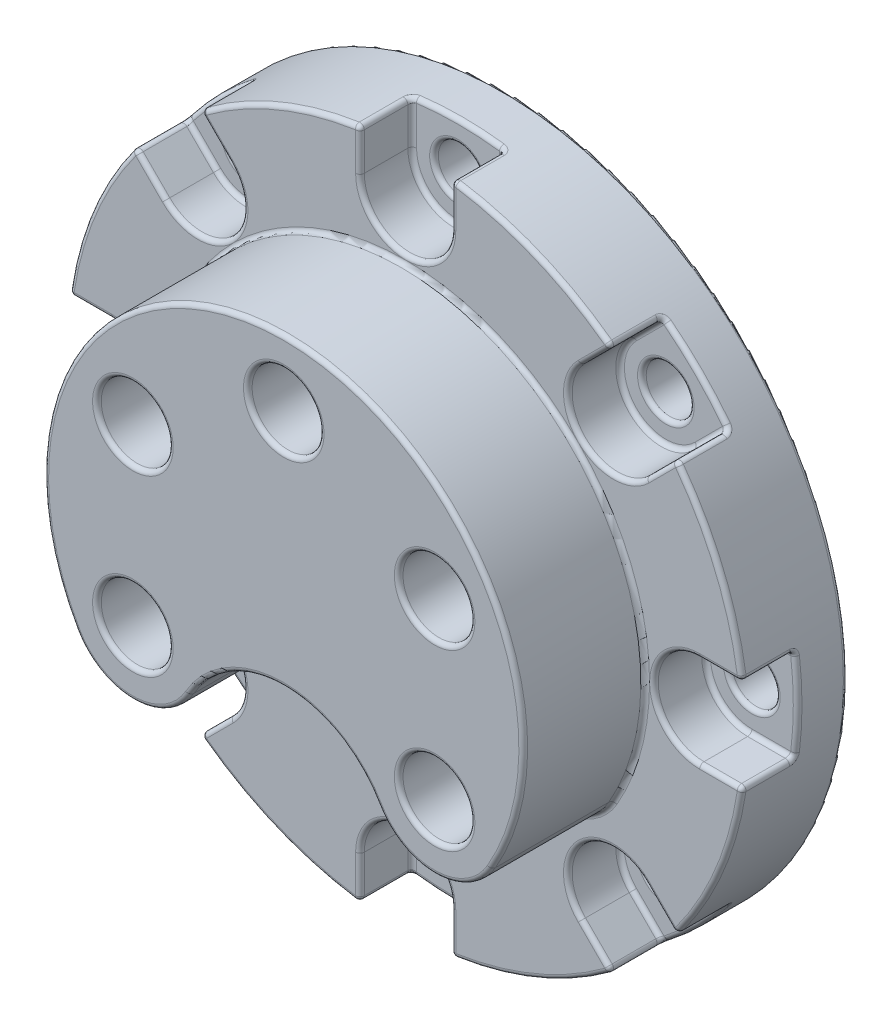
SolidWorks part; units mm, degrees
ref_plane "정면" through (0, 0, 0) normal (0, 0, 1) x (1, 0, 0)
ref_plane "윗면" through (0, 0, 0) normal (0, 1, 0) x (1, 0, 0)
ref_plane "우측면" through (0, 0, 0) normal (1, 0, 0) x (0, 0, -1)
sketch "스케치1" plane through (0, 0, 0) normal (0, 0, 1) x (1, 0, 0)
  circle A0 centre (0, 0) radius 15.6
  circle A1 centre (0, 13.5) radius 1.1
  circle A2 centre (9.5459, 9.5459) radius 1.1
  circle A3 centre (13.5, 0) radius 1.1
  circle A4 centre (9.5459, -9.5459) radius 1.1
  circle A5 centre (0, -13.5) radius 1.1
  circle A6 centre (-9.5459, -9.5459) radius 1.1
  circle A7 centre (-13.5, 0) radius 1.1
  circle A8 centre (-9.5459, 9.5459) radius 1.1
  point P22 (0, 0)
  dimension "D1" = 31.2
  dimension "D2" = 2.2
  dimension "D3" = 13.5
  dimension "D4" = 8
extrude "보스-돌출1" add sketch "스케치1" along normal blind 4.7 contours A0 A8 A7 A6 A5 A4 A3 A2 A1 region at (0, 0, 0)
sketch "스케치2" plane through (0, 0, 4.7) normal (0, 0, 1) x (1, 0, 0)
  line L0 (-2.1, 13.5) -> (-2.1, 15.458)
  line L1 (2.1, 13.5) -> (2.1, 15.458)
  line L2 (11.0309, 8.061) -> (12.4154, 9.4455)
  line L3 (8.061, 11.0309) -> (9.4455, 12.4154)
  line L4 (13.5, -2.1) -> (15.458, -2.1)
  line L5 (13.5, 2.1) -> (15.458, 2.1)
  line L6 (8.061, -11.0309) -> (9.4455, -12.4154)
  line L7 (11.0309, -8.061) -> (12.4154, -9.4455)
  line L8 (-2.1, -13.5) -> (-2.1, -15.458)
  line L9 (2.1, -13.5) -> (2.1, -15.458)
  line L10 (-11.0309, -8.061) -> (-12.4154, -9.4455)
  line L11 (-8.061, -11.0309) -> (-9.4455, -12.4154)
  line L12 (-13.5, 2.1) -> (-15.458, 2.1)
  line L13 (-13.5, -2.1) -> (-15.458, -2.1)
  line L14 (-8.061, 11.0309) -> (-9.4455, 12.4154)
  line L15 (-11.0309, 8.061) -> (-12.4154, 9.4455)
  arc A0 (-2.1, 13.5) -> (2.1, 13.5) centre (0, 13.5) ccw
  circle A1 centre (0, 0) radius 15.6 construction
  arc A2 (2.1, 15.458) -> (-2.1, 15.458) centre (0, 0) ccw
  arc A3 (8.061, 11.0309) -> (11.0309, 8.061) centre (9.5459, 9.5459) ccw
  arc A4 (12.4154, 9.4455) -> (9.4455, 12.4154) centre (0, 0) ccw
  arc A5 (13.5, 2.1) -> (13.5, -2.1) centre (13.5, 0) ccw
  arc A6 (15.458, -2.1) -> (15.458, 2.1) centre (0, 0) ccw
  arc A7 (11.0309, -8.061) -> (8.061, -11.0309) centre (9.5459, -9.5459) ccw
  arc A8 (9.4455, -12.4154) -> (12.4154, -9.4455) centre (0, 0) ccw
  arc A9 (2.1, -13.5) -> (-2.1, -13.5) centre (0, -13.5) ccw
  arc A10 (-2.1, -15.458) -> (2.1, -15.458) centre (0, 0) ccw
  arc A11 (-8.061, -11.0309) -> (-11.0309, -8.061) centre (-9.5459, -9.5459) ccw
  arc A12 (-12.4154, -9.4455) -> (-9.4455, -12.4154) centre (0, 0) ccw
  arc A13 (-13.5, -2.1) -> (-13.5, 2.1) centre (-13.5, 0) ccw
  arc A14 (-15.458, 2.1) -> (-15.458, -2.1) centre (0, 0) ccw
  arc A15 (-11.0309, 8.061) -> (-8.061, 11.0309) centre (-9.5459, 9.5459) ccw
  arc A16 (-9.4455, 12.4154) -> (-12.4154, 9.4455) centre (0, 0) ccw
  point P45 (0, 0)
  dimension "D1" = 4.2
  dimension "D2" = 8
extrude "컷-돌출1" cut sketch "스케치2" against normal blind 2.4
sketch "스케치3" plane through (0, 0, 4.7) normal (0, 0, 1) x (1, 0, 0)
  arc A0 (9.5263, -5.5) -> (-9.5263, -5.5) centre (0, 0) ccw
  circle A1 centre (0, 8) radius 1.65
  circle A2 centre (6.9282, 4) radius 1.65
  circle A3 centre (6.9282, -4) radius 1.65
  circle A4 centre (0, -8) radius 1.65 construction
  circle A5 centre (-6.9282, -4) radius 1.65
  circle A6 centre (-6.9282, 4) radius 1.65
  arc A7 (-9.5263, -5.5) -> (-4.3301, -5.5) centre (-6.9282, -4) ccw
  arc A8 (4.3301, -5.5) -> (9.5263, -5.5) centre (6.9282, -4) ccw
  arc A9 (4.3301, -5.5) -> (-4.3301, -5.5) centre (0, -8) ccw
  point P17 (0, 0)
  dimension "D1" = 22
  dimension "D2" = 3.3
  dimension "D3" = 8
  dimension "D4" = 6
extrude "보스-돌출2" add sketch "스케치3" along normal blind 5.6 contours A9 A8 A0 A7 A6 A5 A3 A2 A1 region at (0, 1.9672, 4.7)
fillet "필렛1" radius 0.2 110 edges at (15.458, 2.1, 3.5) (15.458, -2.1, 3.5) (9.4455, 12.4154, 3.5) (12.4154, 9.4455, 3.5) (-2.1, 15.458, 3.5) (2.1, 15.458, 3.5) (12.4154, -9.4455, 3.5) (9.4455, -12.4154, 3.5) (2.1, -15.458, 3.5) (-2.1, -15.458, 3.5) (-9.4455, -12.4154, 3.5) (-12.4154, -9.4455, 3.5) (-15.458, -2.1, 3.5) (-15.458, 2.1, 3.5) (-12.4154, 9.4455, 3.5) (-9.4455, 12.4154, 3.5) (1.65, 8, 10.3) (8.5782, 4, 10.3) (8.5782, -4, 10.3) (-5.2782, -4, 10.3) (-5.2782, 4, 10.3) (-6.9282, -7, 10.3) (0, 11, 10.3) (6.9282, -7, 10.3) (0, -3, 10.3) (6.9282, -7, 4.7) (0, 11, 4.7) (-6.9282, -7, 4.7) (0, -3, 4.7) (-8.061, 8.061, 4.7) (-8.7533, 11.7231, 4.7) (-5.9699, 14.4125, 4.7) (-2.1, 14.479, 4.7) (0, 11.4, 4.7) (2.1, 14.479, 4.7) (5.9699, 14.4125, 4.7) (8.7533, 11.7231, 4.7) (8.061, 8.061, 4.7) (11.7231, 8.7533, 4.7) (14.4125, 5.9699, 4.7) (14.479, 2.1, 4.7) (11.4, 0, 4.7) (14.479, -2.1, 4.7) (14.4125, -5.9699, 4.7) (11.7231, -8.7533, 4.7) (8.061, -8.061, 4.7) (8.7533, -11.7231, 4.7) (5.9699, -14.4125, 4.7) (2.1, -14.479, 4.7) (0, -11.4, 4.7) (-2.1, -14.479, 4.7) (-5.9699, -14.4125, 4.7) (-8.7533, -11.7231, 4.7) (-8.061, -8.061, 4.7) (-11.7231, -8.7533, 4.7) (-14.4125, -5.9699, 4.7) (-14.479, -2.1, 4.7) (-11.4, 0, 4.7) (-14.479, 2.1, 4.7) (-14.4125, 5.9699, 4.7) (-11.7231, 8.7533, 4.7) (14.479, 2.1, 2.3) (15.6, 0, 2.3) (14.479, -2.1, 2.3) (11.4, 0, 2.3) (14.6, 0, 2.3) (8.7533, 11.7231, 2.3) (11.0309, 11.0309, 2.3) (11.7231, 8.7533, 2.3) (8.061, 8.061, 2.3) (10.6459, 9.5459, 2.3) (-2.1, 14.479, 2.3) (0, 15.6, 2.3) (2.1, 14.479, 2.3) (0, 11.4, 2.3) (1.1, 13.5, 2.3) (11.7231, -8.7533, 2.3) (11.0309, -11.0309, 2.3) (8.7533, -11.7231, 2.3) (8.061, -8.061, 2.3) (10.6459, -9.5459, 2.3) (2.1, -14.479, 2.3) (0, -15.6, 2.3) (-2.1, -14.479, 2.3) (0, -11.4, 2.3) (1.1, -13.5, 2.3) (-8.7533, -11.7231, 2.3) (-11.0309, -11.0309, 2.3) (-11.7231, -8.7533, 2.3) (-8.061, -8.061, 2.3) (-8.4459, -9.5459, 2.3) (-14.479, -2.1, 2.3) (-15.6, 0, 2.3) (-14.479, 2.1, 2.3) (-11.4, 0, 2.3) (-12.4, 0, 2.3) (-11.7231, 8.7533, 2.3) (-11.0309, 11.0309, 2.3) (-8.7533, 11.7231, 2.3) (-8.061, 8.061, 2.3) (-8.4459, 9.5459, 2.3) (15.6, 0, 0) (1.1, 13.5, 0) (10.6459, 9.5459, 0) (14.6, 0, 0) (10.6459, -9.5459, 0) (1.1, -13.5, 0) (-8.4459, -9.5459, 0) (-12.4, 0, 0) (-8.4459, 9.5459, 0)
